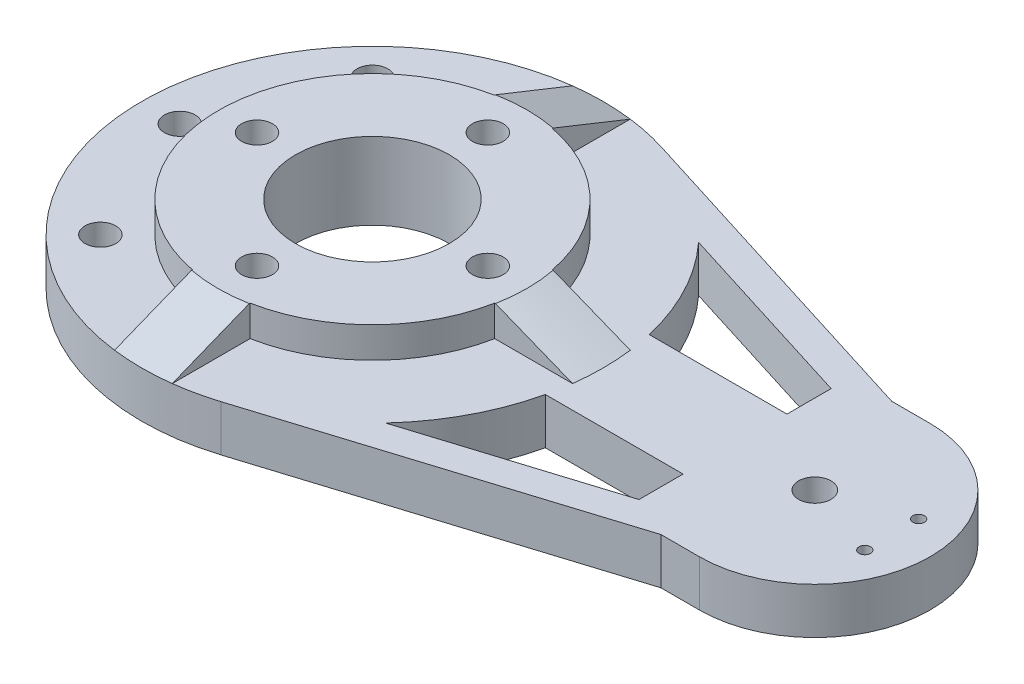
SolidWorks part; units mm, degrees
ref_plane "Front Plane" through (0, 0, 0) normal (0, 0, 1) x (1, 0, 0)
ref_plane "Top Plane" through (0, 0, 0) normal (0, 1, 0) x (1, 0, 0)
ref_plane "Right Plane" through (0, 0, 0) normal (1, 0, 0) x (0, 0, -1)
sketch "Sketch1" plane through (0, 0, 0) normal (0, 1, 0) x (1, 0, 0)
  circle A0 centre (0, 0) radius 20
  circle A1 centre (0, 0) radius 40
  dimension "D1" = 40
  dimension "D2" = 80
extrude "Boss-Extrude1" add sketch "Sketch1" along normal blind 8
sketch "Sketch3" plane through (0, 0, 0) normal (0, -1, 0) x (1, 0, 0)
  line L0 (17.9258, 57.2596) -> (105, 30)
  line L1 (105, 30) -> (105, -30)
  line L2 (105, -30) -> (17.9258, -57.2596)
  arc A0 (17.9258, 57.2596) -> (17.9258, -57.2596) centre (0, 0) ccw
  circle A2 centre (0, 0) radius 20
  circle A3 centre (0, 0) radius 20 construction
  point P6 (105, 0)
  dimension "D3" = 60
  dimension "D1" = 60
  dimension "D2" = 105
extrude "Boss-Extrude2" add sketch "Sketch3" along normal blind 12
sketch "Sketch5" plane through (0, -12, 0) normal (0, -1, 0) x (1, 0, 0)
  circle A0 centre (0, 30) radius 7.5
  circle A1 centre (30, 0) radius 7.5
  circle A2 centre (0, -30) radius 7.5
  circle A3 centre (-30, 0) radius 7.5
  point P12 (0, 0)
  dimension "D1" = 15
  dimension "D2" = 30
  dimension "D3" = 4
extrude "Cut-Extrude3" cut sketch "Sketch5" against normal blind 10
sketch "Sketch2" plane through (0, 8, 0) normal (0, 1, 0) x (1, 0, 0)
  circle A0 centre (30, 0) radius 4
  circle A1 centre (0, -30) radius 4
  circle A2 centre (-30, 0) radius 4
  circle A3 centre (0, 30) radius 4
  point P12 (0, 0)
  dimension "D1" = 8
  dimension "D2" = 30
  dimension "D3" = 4
extrude "Cut-Extrude1" cut sketch "Sketch2" against normal up to surface (20 mm away) up to face at (0, -12, 22.5)
sketch "Sketch6" plane through (0, 0, 0) normal (0, 1, 0) x (1, 0, 0)
  line L0 (-7.5, -39.2906) -> (-7.5, -59.5294)
  line L1 (7.5, -39.2906) -> (7.5, -59.5294)
  line L4 (-7.5, 39.2906) -> (-7.5, 59.5294)
  line L5 (7.5, 39.2906) -> (7.5, 59.5294)
  line L6 (39.2906, 7.5) -> (59.5294, 7.5)
  line L7 (39.2906, -7.5) -> (59.5294, -7.5)
  line L8 (-39.2906, -7.5) -> (-59.5294, -7.5) [skipped]
  line L9 (-39.2906, 7.5) -> (-59.5294, 7.5) [skipped]
  arc A0 (-7.5, -39.2906) -> (7.5, -39.2906) centre (0, 0) ccw
  circle A1 centre (0, 0) radius 40 construction
  arc A2 (-7.5, -59.5294) -> (7.5, -59.5294) centre (0, 0) ccw
  arc A3 (17.9258, 57.2596) -> (17.9258, -57.2596) centre (0, 0) ccw construction
  arc A6 (7.5, 59.5294) -> (-7.5, 59.5294) centre (0, 0) ccw
  arc A7 (7.5, 39.2906) -> (-7.5, 39.2906) centre (0, 0) ccw
  arc A8 (59.5294, -7.5) -> (59.5294, 7.5) centre (0, 0) ccw
  arc A9 (39.2906, -7.5) -> (39.2906, 7.5) centre (0, 0) ccw
  arc A10 (-59.5294, 7.5) -> (-59.5294, -7.5) centre (0, 0) ccw [skipped]
  arc A11 (-39.2906, 7.5) -> (-39.2906, -7.5) centre (0, 0) ccw [skipped]
  point P11 (0, -60)
  point P12 (0, -40)
  point P28 (0, 0)
  dimension "D1" = 15
  dimension "D2" = 4
extrude "Boss-Extrude3" add sketch "Sketch6" along normal up to surface (8 mm away) up to face at (30, 8, 4)
chamfer "Chamfer1" distance 8 angle 68 3 edges at (0, 8, -60) (60, 8, 0) (0, 8, 60) first distance on face at (-4.8851, 0.6667, 0) first distance on face at (59.7647, 4, 0)
sketch "Sketch7" plane through (0, -12, 0) normal (0, -1, 0) x (1, 0, 0)
  line L2 (115, 30) -> (105, 30)
  line L3 (105, -30) -> (105, 30) construction
  line L4 (105, 30) -> (105, -30)
  line L5 (105, -30) -> (115, -30)
  arc A0 (115, 30) -> (115, -30) centre (115, 0) cw
  point P3 (105, 0)
  point P5 (105, 0)
  dimension "D1" = 60
  dimension "D2" = 10
extrude "Boss-Extrude4" add sketch "Sketch7" against normal up to surface (12 mm away) up to face at (40.3201, 0, 0)
sketch "Sketch8" plane through (0, -12, 0) normal (0, -1, 0) x (1, 0, 0)
  line L1 (111.2472, -6.5) -> (118.7528, -6.5)
  line L2 (118.7528, -6.5) -> (122.5056, 0)
  line L3 (122.5056, 0) -> (118.7528, 6.5)
  line L4 (118.7528, 6.5) -> (111.2472, 6.5)
  line L5 (111.2472, 6.5) -> (107.4944, 0)
  line L6 (107.4944, 0) -> (111.2472, -6.5)
  circle A0 centre (115, 0) radius 6.5 construction
  arc A1 (115, -30) -> (115, 30) centre (115, 0) ccw construction
  point P13 (145, 0)
  dimension "D1" = 13
extrude "Cut-Extrude4" cut sketch "Sketch8" against normal blind 6
sketch "Sketch9" plane through (0, -6, 0) normal (0, -1, 0) x (1, 0, 0)
  circle A0 centre (115, 0) radius 4.2
  dimension "D1" = 8.4
extrude "Cut-Extrude5" cut sketch "Sketch9" against normal up to surface (6 mm away) up to face at (-28.75, 0, 0)
sketch "Sketch11" plane through (0, 0, 0) normal (0, 1, 0) x (1, 0, 0)
  line L1 (94.2688, 24.9767) -> (94.2688, 13.5)
  line L2 (94.2688, 13.5) -> (58.4615, 13.5)
  line L5 (44.1018, 40.682) -> (94.2688, 24.9767)
  line L6 (17.9258, 57.2596) -> (105, 30) construction
  line L8 (59.5294, 7.5) -> (39.2906, 7.5) construction
  arc A0 (58.4615, 13.5) -> (44.1018, 40.682) centre (0, 0) ccw
  dimension "D1" = 60
  dimension "D2" = 8
  dimension "D4" = 6
extrude "Cut-Extrude7" cut sketch "Sketch11" against normal up to surface (12 mm away) up to face at (115, -12, 0)
mirror "Mirror1" about plane through (0, 0, 0) normal (0, 0, 1) of "Cut-Extrude7"
sketch "草图1" plane through (0, 0, 0) normal (0, 1, 0) x (1, 0, 0)
  line L0 (-45.8579, -14.1421) -> (-60, 0) construction
  line L1 (-45.8579, 14.1421) -> (-60, 0) construction
  circle A0 centre (-35.3553, 35.3553) radius 4
  circle A1 centre (-35.3553, -35.3553) radius 4
  circle A2 centre (-50, -0.0682) radius 4
  arc A3 (-7.5, 59.5294) -> (-7.5, -59.5294) centre (0, 0) ccw construction
  arc A5 (-7.5, 59.5294) -> (-7.5, -59.5294) centre (0, 0) ccw construction
  arc A6 (-7.5, 39.2906) -> (-7.5, -39.2906) centre (0, 0) ccw construction
  point P8 (0, 0)
  point P21 (-60, 0)
  dimension "D1" = 50
  dimension "D2" = 50
extrude "切除-拉伸1" cut sketch "草图1" against normal through all contours A1 | A0
sketch "草图2" plane through (0, 0, 0) normal (0, 1, 0) x (1, 0, 0)
  line L0 (135, -7) -> (135, 7) construction
  line L1 (115, 0) -> (135, 0) construction
  circle A0 centre (135, -7) radius 1.5
  circle A2 centre (135, 7) radius 1.5
  circle A3 centre (115, 0) radius 4.2 construction
  point P3 (135, 0)
  dimension "D1" = 3
  dimension "D2" = 20
  dimension "D3" = 14
extrude "切除-拉伸2" cut sketch "草图2" against normal through all contours A0 | A2 region at (135, 0, 7)
sketch "草图3" plane through (0, -12, 0) normal (0, -1, 0) x (1, 0, 0)
  line L12 (133.4123, -9.75) -> (136.5877, -9.75)
  line L13 (136.5877, -9.75) -> (138.1754, -7)
  line L14 (138.1754, -7) -> (136.5877, -4.25)
  line L15 (136.5877, -4.25) -> (133.4123, -4.25)
  line L16 (133.4123, -4.25) -> (131.8246, -7)
  line L17 (131.8246, -7) -> (133.4123, -9.75)
  line L18 (133.4123, 4.25) -> (136.5877, 4.25)
  line L19 (136.5877, 4.25) -> (138.1754, 7)
  line L20 (138.1754, 7) -> (136.5877, 9.75)
  line L21 (136.5877, 9.75) -> (133.4123, 9.75)
  line L22 (133.4123, 9.75) -> (131.8246, 7)
  line L23 (131.8246, 7) -> (133.4123, 4.25)
  circle A0 centre (135, -7) radius 2.75 construction
  circle A1 centre (135, -7) radius 1.5 construction
  circle A2 centre (135, 7) radius 2.75 construction
  circle A4 centre (135, 7) radius 1.5 construction
  dimension "D1" = 5.5
  dimension "D2" = 5.5
extrude "切除-拉伸3" cut sketch "草图3" against normal blind 3.5
extrude "切除-拉伸4" cut sketch "草图1<4>" against normal through all
sketch "草图1<4>" plane through (0, 0, 0) normal (0, 1, 0) x (1, 0, 0) same geometry as "草图1"
